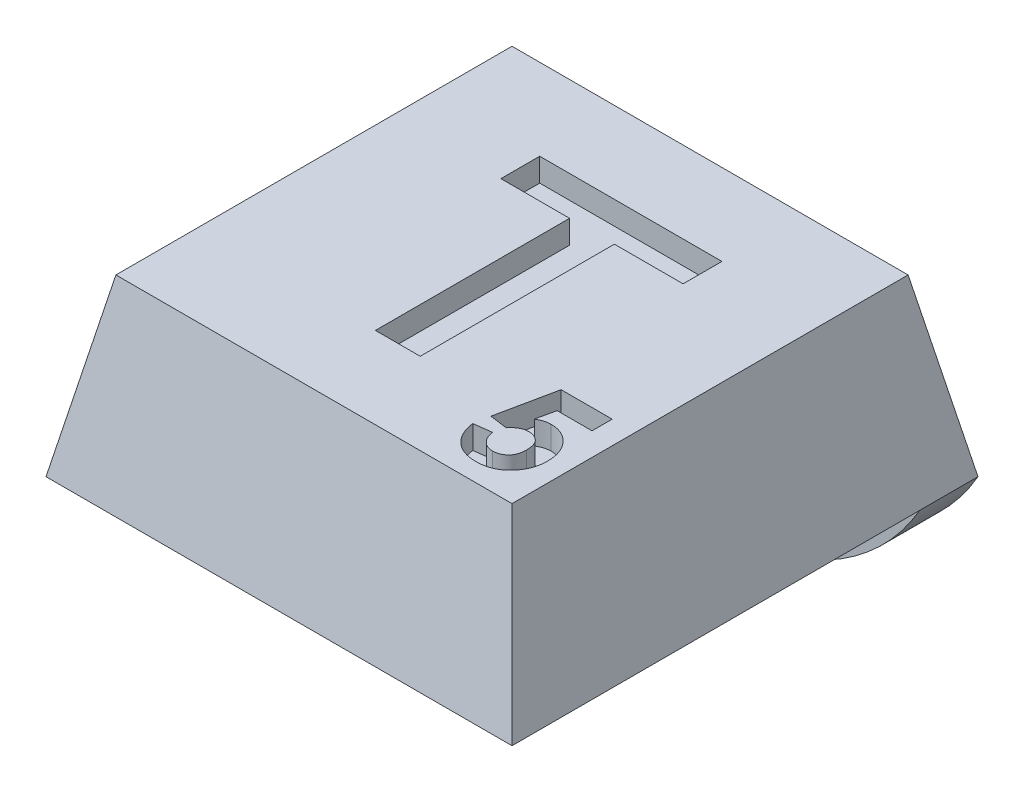
SolidWorks part; units mm, degrees
ref_plane "Front Plane" through (0, 0, 0) normal (0, 0, 1) x (1, 0, 0)
ref_plane "Top Plane" through (0, 0, 0) normal (0, 1, 0) x (1, 0, 0)
ref_plane "Right Plane" through (0, 0, 0) normal (1, 0, 0) x (0, 0, -1)
sketch "Sketch1" plane through (0, 0, 0) normal (0, 1, 0) x (1, 0, 0)
  line L1 (0, 0) -> (8, 0)
  line L2 (0, 0) -> (0, 8)
  line L3 (0, 8) -> (8, 8)
  line L4 (8, 0) -> (8, 8)
  dimension "D1" = 8
  dimension "D2" = 8
extrude "Boss-Extrude1" add sketch "Sketch1" along normal blind 3
sketch "Sketch2" plane through (0, 0, 0) normal (0, 0, 1) x (1, 0, 0)
  line L0 (0, 0) -> (0.6, 3)
  line L1 (0, 3) -> (8, 3) construction
  line L2 (0.6, 3) -> (0, 3)
  line L3 (0, 3) -> (0, 0)
  line L4 (8, 0) -> (7.4, 3)
  line L5 (7.4, 3) -> (8, 3)
  line L6 (8, 3) -> (8, 0)
  dimension "D1" = 0.6
  dimension "D2" = 0.6
extrude "Cut-Extrude1" cut sketch "Sketch2" against normal through all both and the other way through all
sketch "Sketch3" plane through (0, 0, 0) normal (1, 0, 0) x (0, 0, -1)
  line L0 (0, 0) -> (0.6, 3)
  line L1 (8, 3) -> (0, 3) construction
  line L2 (0.6, 3) -> (0, 3)
  line L3 (0, 3) -> (0, 0)
  line L4 (8, 3) -> (7.4, 3)
  line L5 (7.4, 3) -> (8, 0)
  line L6 (8, 3) -> (8, 0)
  dimension "D1" = 0.6
  dimension "D2" = 0.6
extrude "Cut-Extrude2" cut sketch "Sketch3" along normal blind 11
sketch "Sketch4" plane through (0, 0, 0) normal (0, -1, 0) x (1, 0, 0)
  line L0 (8, 0) -> (8, -8) construction
  line L3 (0, 0) -> (8, 0) construction
  circle A0 centre (4, -3.75) radius 1.8
  dimension "D1" = 3.6
  dimension "D2" = 4
  dimension "D3" = 3.75
extrude "Cut-Extrude3" cut sketch "Sketch4" against normal blind 0.8
sketch "Sketch5" plane through (0, 0, 0) normal (0, -1, 0) x (1, 0, 0)
  line L0 (8, 0) -> (8, -8) construction
  line L1 (0, -8) -> (8, -8)
  line L2 (0, -8) -> (0, -7)
  line L3 (0, -7) -> (8, -7)
  line L4 (8, -8) -> (8, -7)
  dimension "D1" = 1
extrude "Boss-Extrude2" add sketch "Sketch5" along normal blind 2
fillet "Fillet1" radius 4 2 edges at (8, -2, -7.5) (0, -2, -7.5)
sketch "Sketch6" plane through (0, 3, 0) normal (0, 1, 0) x (1, 0, 0)
  text T0 "T" font "Arial" height 4
extrude "Cut-Extrude4" cut sketch "Sketch6" against normal blind 0.4
sketch "Sketch7" plane through (0, 3, 0) normal (0, 1, 0) x (1, 0, 0)
  text T0 "5" font "Arial" height 1.8
extrude "Cut-Extrude5" cut sketch "Sketch7" against normal blind 0.4
